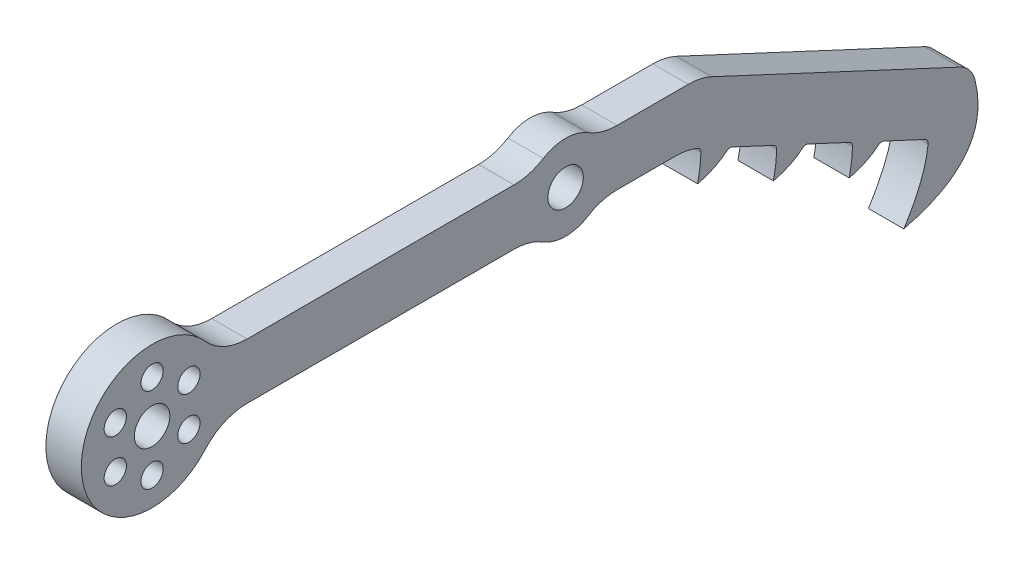
SolidWorks part; units mm, degrees
material "6061 Alloy"
ref_plane "Front Plane" through (0, 0, 0) normal (0, 0, 1) x (1, 0, 0)
ref_plane "Top Plane" through (0, 0, 0) normal (0, 1, 0) x (1, 0, 0)
ref_plane "Right Plane" through (0, 0, 0) normal (1, 0, 0) x (0, 0, -1)
sketch "Sketch1" plane through (0, 0, 0) normal (1, 0, 0) x (0, 0, -1)
  line L0 (-57.9219, 44.5435) -> (-40.0493, 54.8622)
  line L1 (-40.0493, 49.8622) -> (56.1047, 49.8622)
  line L2 (56.1047, 49.8622) -> (102.5472, 28.2057)
  line L3 (-40.0493, 59.8622) -> (58.3217, 59.8622)
  line L4 (58.3217, 59.8622) -> (106.7734, 37.2688)
  line L5 (56.1047, 49.8622) -> (84.5622, 36.5923) construction
  line L6 (58.3217, 59.8622) -> (88.7883, 45.6554) construction
  line L7 (102.5472, 28.2057) -> (106.7734, 37.2688)
  line L8 (102.5472, 28.2057) -> (111.6103, 23.9795)
  line L9 (93.4842, 32.4319) -> (106.7734, 37.2688)
  line L10 (56.1047, 49.8622) -> (58.3217, 59.8622) construction
  circle A0 centre (-57.9219, 44.5435) radius 15.875
  circle A1 centre (-40.0493, 54.8622) radius 4.7625
  circle A2 centre (-40.0493, 54.8622) radius 2.5
  circle A3 centre (-40.0493, 54.8622) radius 5
  circle A4 centre (-40.0493, 54.8622) radius 12.7
  circle A6 centre (34.1047, 54.8622) radius 7.62
  parabola Q0 (106.7734, 37.2688) -> (94.7552, 18.0752) focus (102.5472, 28.2057) apex (107.0788, 26.0926)
  parabola Q1 (99.1632, 29.7837) -> (94.7552, 18.0752) focus (93.4842, 32.4319) apex (98.5101, 34.2612)
  parabola Q2 (93.4202, 43.4955) -> (84.9631, 30.8885) focus (87.9414, 37.2725) apex (91.341, 34.5621)
  parabola Q3 (85.5686, 36.123) -> (84.9631, 30.8885) focus (78.3442, 40.2408) apex (83.762, 43.3694)
  parabola Q4 (79.8256, 49.8348) -> (71.3685, 37.2277) focus (74.3468, 43.6117) apex (77.7464, 40.9013)
  parabola Q5 (71.974, 42.4623) -> (71.3685, 37.2277) focus (64.7496, 46.58) apex (70.1674, 49.7086)
  parabola Q6 (66.2309, 56.1741) -> (57.7739, 43.567) focus (60.7522, 49.951) apex (64.1518, 47.2406)
  parabola Q7 (58.3794, 48.8015) -> (57.7739, 43.567) focus (51.155, 52.9193) apex (56.5728, 56.0479)
  point P12 (93.4842, 32.4319)
  point P19 (100.1288, 34.8504)
  point P46 (57.2132, 54.8622)
  point P47 (34.1047, 54.8622)
  dimension "D1" = 10
  dimension "D5" = 10
  dimension "D2" = 12.4745
  dimension "D3" = 5
  dimension "D4" = 15
  dimension "D6" = 5
  dimension "D7" = 22
extrude "Boss-Extrude1" add sketch "Sketch1" along normal blind 6.35 contours A0 A4 L0 A3 | L0 A4 A0 A3 | A0 A4 L1 A3 | L3 A4 A0 A3 | L0 A3 A0 | A0 A3 L0 | A3 A0 A1 | A2 A1 | A2 | L1 A4 L3 A3 | A6 L3 A4 L1 | L3 A6 L1 | L3 A6 | L1 A6 | Q6 L4 L3 A6 L1 L2 | L2 Q7 Q6 | L4 Q6 L2 Q4 | L2 Q5 Q4 | L4 Q4 L2 Q2 | L2 Q3 Q2 | L4 Q2 L2 L9 | L9 L2 L7 | Q0 L7 L8 | L2 Q1 Q0 L8 | A6 region at (0, 53.7938, 49.4225) region at (0, 47.279, 45.6612) region at (0, 52.862, 44.5166) region at (0, 51.9936, 44.0152) region at (0, 62.2646, 41.1006) region at (0, 46.6449, 36.6917) region at (0, 57.2087, 40.6781) region at (0, 53.0598, 44.5079) region at (0, 59.3323, 41.2471) region at (0, 54.8622, 31.9722) region at (0, 54.8622, 0.304) region at (0, 60.9274, -34.1047) region at (0, 54.8622, -34.1047) region at (0, 48.7971, -34.1047) region at (0, 54.2453, -53.6216) region at (0, 47.8087, -72.3396) region at (0, 46.1053, -60.0268) region at (0, 41.4694, -85.9342) region at (0, 37.45, -97.3772) region at (0, 39.7661, -73.6214) region at (0, 30.7591, -105.9447) region at (0, 32.6355, -100.9349) region at (0, 33.4268, -87.216) region at (0, 23.9786, -100.9688)
sketch "Sketch7" plane through (6.35, 0, 0) normal (1, 0, 0) x (0, 0, -1)
  point P0 (-40.0493, 54.8622)
  point P1 (34.1047, 54.8622)
hole_wizard "1/4 (0.2500) Dowel Hole4" positions "Sketch7" profile "Sketch8" hole size "1/4" standard "ANSI Inch" end condition through all
sketch "Sketch8" plane through (6.35, 54.8622, 40.0493) normal (0, 1, 0) x (0, 0, -1)
  line L0 (0, 0) -> (0, 6.35)
  line L1 (0, 6.35) -> (3.175, 6.35)
  line L2 (3.175, 6.35) -> (3.175, 0)
  line L5 (3.175, 0) -> (0, 0)
  line L11 (0, -6.35) -> (0, 107.95) construction
  dimension "Thru Hole Dia." = 6.35
  dimension "Thru Hole Depth" = 6.35
fillet "Fillet1" radius 10 2 edges at (3.175, 59.8622, 28.375) (3.175, 49.8622, 28.375)
fillet "Fillet2" radius 10 2 edges at (3.175, 49.8622, -56.1047) (3.175, 59.8622, -58.3217)
fillet "Fillet4" radius 5 1 edges at (3.175, 37.2688, -106.7734)
fillet "Fillet5" radius 1 7 edges at (3.175, 33.7664, -90.6224) (3.175, 40.1057, -77.0278) (3.175, 46.4449, -63.4331) (3.175, 48.8015, -58.3794) (3.175, 42.4623, -71.974) (3.175, 36.123, -85.5686) (3.175, 29.7837, -99.1632)
fillet "Fillet6" radius 10 4 edges at (3.175, 49.8622, -28.3545) (3.175, 49.8622, -39.8549) (3.175, 59.8622, -28.3545) (3.175, 59.8622, -39.8549)
sketch "Sketch9" plane through (6.35, 0, 0) normal (1, 0, 0) x (0, 0, -1)
  point P0 (-40.0493, 54.8622)
  point P1 (-40.0493, 62.7997)
  point P6 (-33.1752, 50.8935)
  point P7 (-46.9234, 50.8935)
  point P8 (-40.0493, 54.8622)
  dimension "D1" = 7.9375
  dimension "D2" = 3
sketch "Sketch10" plane through (6.35, 0, 0) normal (1, 0, 0) x (0, 0, -1)
  point P0 (-40.0493, 62.4822)
  point P1 (-40.0493, 54.8622)
  point P5 (-40.0493, 54.8622)
  dimension "D1" = 7.62
hole_wizard "Ø4.0mm Dowel Hole1" positions "Sketch10" profile "Sketch11" hole size "Ø4.0" standard "ANSI Metric" end condition through all
sketch "Sketch11" plane through (6.35, 62.4822, 40.0493) normal (0, 1, 0) x (0, 0, -1)
  line L0 (0, 0) -> (0, 6.35)
  line L1 (0, 6.35) -> (2, 6.35)
  line L2 (2, 6.35) -> (2, 0)
  line L5 (2, 0) -> (0, 0)
  line L11 (0, -6.35) -> (0, 107.95) construction
  dimension "Thru Hole Dia." = 4
  dimension "Thru Hole Depth" = 6.35
pattern_circular "CirPattern1" count 6 over 360 about axis through (6.35, 54.8622, 40.0493) along (1, 0, 0) of "Ø4.0mm Dowel Hole1"
